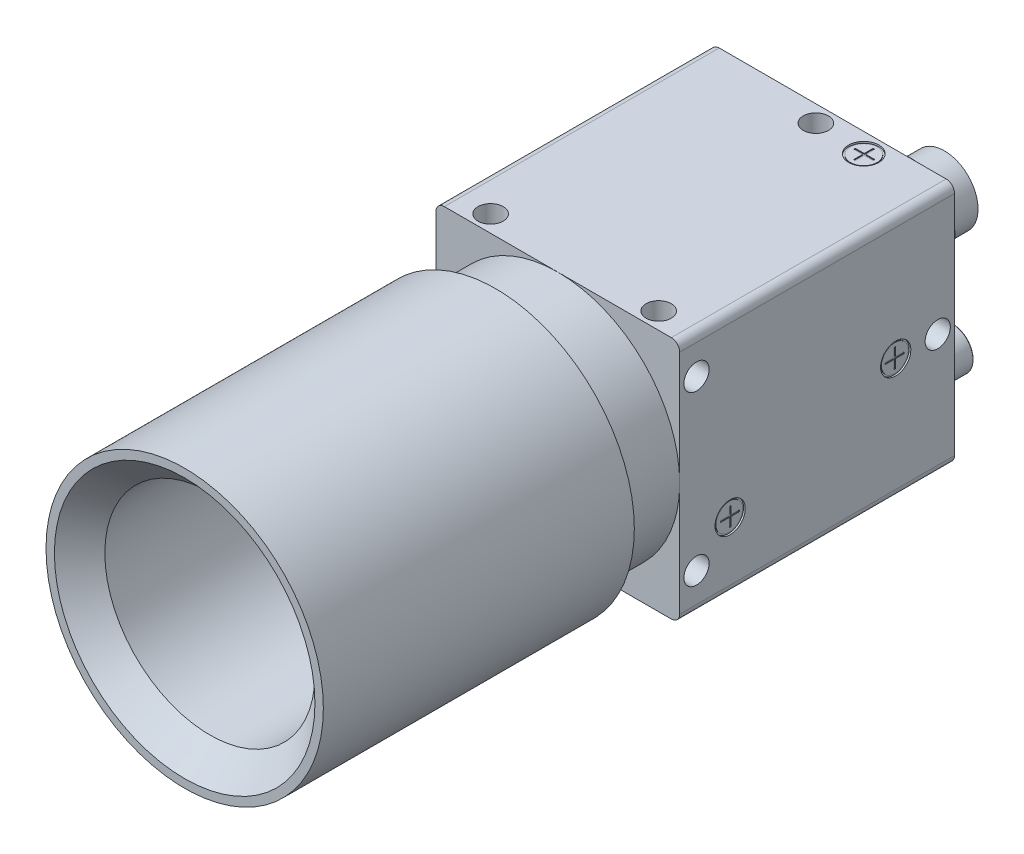
SolidWorks part; units mm, degrees
ref_plane "前视基准面" through (0, 0, 0) normal (0, 0, 1) x (1, 0, 0)
ref_plane "上视基准面" through (0, 0, 0) normal (0, 1, 0) x (1, 0, 0)
ref_plane "右视基准面" through (0, 0, 0) normal (1, 0, 0) x (0, 0, -1)
sketch "草图2" plane through (0, 0, 0) normal (0, 0, 1) x (1, 0, 0)
  line L1 (-14.5, 14.5) -> (14.5, 14.5)
  line L2 (-14.5, 14.5) -> (-14.5, -14.5)
  line L3 (-14.5, -14.5) -> (14.5, -14.5)
  line L4 (14.5, 14.5) -> (14.5, -14.5)
  line L5 (-14.5, 14.5) -> (14.5, -14.5) construction
  line L6 (-14.5, -14.5) -> (14.5, 14.5) construction
  point P0 (0, 0)
  dimension "D1" = 29
  dimension "D2" = 29
extrude "凸台-拉伸1" add sketch "草图2" along normal blind 32.7
sketch "草图3" plane through (0, 0, 32.7) normal (0, 0, 1) x (1, 0, 0)
  circle A0 centre (0, 0) radius 14.5
  circle A1 centre (0, 0) radius 12.5
  dimension "D1" = 29
  dimension "D2" = 25
extrude "凸台-拉伸2" add sketch "草图3" along normal blind 7.4
sketch "草图4" plane through (0, 0, 32.7) normal (0, 0, 1) x (1, 0, 0)
  line L0 (6, 7.5) -> (7.5, 6)
  line L1 (-6, 7.5) -> (6, 7.5)
  line L2 (-7.5, 6) -> (-7.5, -6)
  line L3 (-6, -7.5) -> (6, -7.5)
  line L4 (7.5, 6) -> (7.5, -6)
  line L5 (-6.75, 6.75) -> (6.75, -6.75) construction
  line L6 (-6.75, -6.75) -> (6.75, 6.75) construction
  line L7 (-6, 7.5) -> (-7.5, 6)
  line L8 (0, 0) -> (10.6258, 0) construction
  line L9 (6, -7.5) -> (7.5, -6)
  line L10 (-6, -7.5) -> (-7.5, -6)
  point P0 (0, 0)
  dimension "D1" = 6
  dimension "D2" = 7.5
  dimension "D3" = 6
  dimension "D4" = 45
  dimension "D5" = 45
  dimension "D6" = 7.5
  dimension "D7" = 7.5
extrude "切除-拉伸1" cut sketch "草图4" against normal blind 5
chamfer "倒角1" distance 1 angle 45 8 edges at (-7.5, 0, 32.7) (-6.75, -6.75, 32.7) (0, -7.5, 32.7) (6.75, -6.75, 32.7) (7.5, 0, 32.7) (6.75, 6.75, 32.7) (0, 7.5, 32.7) (-6.75, 6.75, 32.7)
sketch "草图5" plane through (0, 0, 32.7) normal (0, 0, 1) x (1, 0, 0)
  line L0 (6.4142, -8.5) -> (-6.4142, -8.5) construction
  line L5 (-2, -10.5) -> (-2, -12.339)
  line L6 (2, -10.5) -> (2, -12.339)
  arc A0 (2, -10.5) -> (-2, -10.5) centre (0, -10.5) ccw
  circle A1 centre (0, 0) radius 12.5 construction
  circle A2 centre (0, 0) radius 12.5 construction
  arc A3 (-2, -12.339) -> (2, -12.339) centre (0, 0) ccw
  circle M14 centre (0, 0) radius 12.5
extrude "切除-拉伸2" cut sketch "草图5" against normal blind 1 contours L6 A0 L5 M14 region at (0, -10.6598, 32.7)
sketch "草图7" plane through (0, 0, 31.7) normal (0, 0, 1) x (1, 0, 0)
  circle A0 centre (0, -10.5) radius 1.8
  dimension "D1" = 3.6
extrude "凸台-拉伸6" add sketch "草图7" along normal blind 0.8
fillet "圆角1" radius 0.2 1 edges at (1.8, -10.5, 32.5)
sketch "草图8" plane through (0, 0, 32.5) normal (0, 0, 1) x (1, 0, 0)
  line L0 (0, -9.5) -> (0, -11.5)
  line L2 (-1, -10.5) -> (1, -10.5)
  circle A0 centre (0, -10.5) radius 1.6 construction
  point P3 (0, -10.5)
  point P8 (0, -10.5)
  dimension "D1" = 2
  dimension "D2" = 2
extrude "切除-拉伸-薄壁1" cut sketch "草图8" against normal blind 0.2 thin thin type mid plane wall 0.2
fillet "圆角2" radius 0.2 4 edges at (-0.1, -10.6, 32.4) (0.1, -10.6, 32.4) (0.1, -10.4, 32.4) (-0.1, -10.4, 32.4)
fillet "圆角3" radius 0.1 8 edges at (-1, -10.4, 32.4) (-0.1, -11.5, 32.4) (0.1, -11.5, 32.4) (-1, -10.6, 32.4) (1, -10.6, 32.4) (1, -10.4, 32.4) (0.1, -9.5, 32.4) (-0.1, -9.5, 32.4)
mirror "镜向2" about plane through (0, 0, 0) normal (0, 1, 0) of "切除-拉伸2"
mirror "镜向1" about plane through (0, 0, 0) normal (0, 1, 0) of "圆角3", "切除-拉伸-薄壁1", "凸台-拉伸6"
fillet "圆角4" radius 1 4 edges at (-14.5, -14.5, 16.35) (14.5, -14.5, 16.35) (14.5, 14.5, 16.35) (-14.5, 14.5, 16.35)
sketch "草图9" plane through (0, -14.5, 0) normal (0, -1, 0) x (1, 0, 0)
  line L0 (-13.5, 16.35) -> (13.5, 16.35) construction
  line L1 (-13.5, 32.7) -> (-13.5, 0) construction
  line L2 (13.5, 0) -> (13.5, 32.7) construction
  line L3 (0, 0) -> (0, 32.7) construction
  line L4 (0, 32.7) -> (-14.5, 32.7) construction
  circle A0 centre (-10, 2) radius 1.5
  circle A1 centre (-10, 30.7) radius 1.5
  circle A2 centre (10, 30.7) radius 1.5
  circle A3 centre (10, 2) radius 1.5
  dimension "D1" = 3
  dimension "D2" = 28.7
  dimension "D3" = 10
sketch "草图10" plane through (0, -14.5, 0) normal (0, -1, 0) x (1, 0, 0)
  line L0 (-12, 5) -> (12, 5)
  line L1 (-13.5, 32.7) -> (-13.5, 0) construction
  line L3 (-13.5, 0) -> (13.5, 0) construction
  line L5 (-11, 25) -> (11, 25)
  line L6 (-12, 24) -> (-12, 6)
  line L7 (-11, 5) -> (11, 5)
  line L8 (12, 24) -> (12, 6)
  line L9 (-12, 25) -> (12, 5) construction
  line L10 (-12, 5) -> (12, 25) construction
  arc A0 (11, 25) -> (12, 24) centre (11, 24) cw
  arc A1 (-12, 6) -> (-11, 5) centre (-11, 6) ccw
  arc A2 (-11, 25) -> (-12, 24) centre (-11, 24) ccw
  arc A3 (11, 5) -> (12, 6) centre (11, 6) ccw
  point P8 (0, 15)
  dimension "D4" = 1
  dimension "D1" = 5
  dimension "D2" = 1.5
  dimension "D3" = 20
extrude "切除-拉伸4" cut sketch "草图10" against normal blind 0.1 contours L0 A3 L8 A0 L5 A2 L6 A1 region at (0, -14.5, 15)
extrude "切除-拉伸6" cut sketch "草图9" against normal blind 4
sketch "草图12" plane through (0, -14.4, 0) normal (0, -1, 0) x (1, 0, 0)
  line L0 (-11, 5) -> (11, 5) construction
  line L1 (-12, 24) -> (-12, 6) construction
  line L2 (12, 24) -> (12, 6) construction
  line L3 (-11, 5) -> (11, 5) construction
  line L4 (0, 25) -> (0, 32.7) construction
  line L5 (-11, 25) -> (11, 25) construction
  line L6 (0, 32.7) -> (-14.5, 32.7) construction
  circle A0 centre (-10, 7.6) radius 1.8
  circle A1 centre (10, 7.6) radius 1.8
  circle A2 centre (-5, 28.9) radius 1.8
  circle A3 centre (5, 28.9) radius 1.8
  dimension "D1" = 3.6
  dimension "3.6" = 3.6
  dimension "D8" = 3.6
  dimension "D9" = 3.6
  dimension "D2" = 2.6
  dimension "D3" = 2
  dimension "D4" = 2
  dimension "D5" = 2.6
  dimension "D6" = 3.8
  dimension "D7" = 5
extrude "切除-拉伸7" cut sketch "草图12" against normal mid plane 0.4
sketch "草图13" plane through (0, -14.2, 0) normal (0, -1, 0) x (1, 0, 0)
  circle A0 centre (-10, 7.6) radius 1.6
  circle A1 centre (10, 7.6) radius 1.6
  circle A2 centre (5, 28.9) radius 1.6
  circle A3 centre (-5, 28.9) radius 1.6
  dimension "D1" = 3.2
extrude "凸台-拉伸8" add sketch "草图13" along normal blind 0.1
sketch "草图14" plane through (0, -14.3, 0) normal (0, -1, 0) x (1, 0, 0)
  line L0 (-10, 6.3075) -> (-10, 8.7975)
  line L2 (-11.3258, 7.6) -> (-8.7234, 7.6)
extrude "切除-拉伸-薄壁2" cut sketch "草图14" against normal blind 0.1 thin thin type mid plane wall 0.2
mirror "镜向3" about plane through (0, 0, 0) normal (1, 0, 0) of "切除-拉伸-薄壁2"
sketch "草图16" plane through (0, -14.3, 0) normal (0, -1, 0) x (1, 0, 0)
  line L0 (-5, 27.7633) -> (-5, 30.1768)
  line L2 (-6.2768, 28.9) -> (-3.9542, 28.9)
extrude "切除-拉伸-薄壁4" cut sketch "草图16" against normal blind 0.1 thin thin type mid plane wall 0.2
mirror "镜向4" about plane through (0, 0, 0) normal (1, 0, 0) of "切除-拉伸-薄壁4"
sketch "草图17" plane through (14.5, 0, 0) normal (1, 0, 0) x (0, 0, -1)
  line L0 (0, 0) -> (-32.7, 0) construction
  line L1 (-16.35, -13.5) -> (-16.35, 13.5) construction
  line L2 (-32.7, -13.5) -> (0, -13.5) construction
  line L3 (0, 13.5) -> (-32.7, 13.5) construction
  line L4 (-32.7, -13.5) -> (-32.7, 0) construction
  circle A0 centre (-2, 0) radius 1.5
  circle A1 centre (-30.7, -10) radius 1.5
  circle A2 centre (-30.7, 10) radius 1.5
  dimension "D1" = 3
  dimension "D2" = 3
  dimension "D5" = 3
  dimension "D3" = 20
  dimension "D4" = 2
  dimension "D6" = 28.7
extrude "切除-拉伸8" cut sketch "草图17" against normal blind 4
sketch "草图18" plane through (14.5, 0, 0) normal (1, 0, 0) x (0, 0, -1)
  line L0 (-32.7, -13.5) -> (-32.7, 0) construction
  line L1 (-32.7, -13.5) -> (0, -13.5) construction
  circle A0 centre (-7, 0) radius 1.8
  circle A1 centre (-26.7, -6.5) radius 1.8
  dimension "D1" = 3.6
  dimension "D2" = 3.6
  dimension "D3" = 7
  dimension "D4" = 6
  dimension "D5" = 7
extrude "切除-拉伸9" cut sketch "草图18" against normal blind 0.2
sketch "草图19" plane through (14.3, 0, 0) normal (1, 0, 0) x (0, 0, -1)
  circle A0 centre (-7, 0) radius 1.6
  circle A1 centre (-26.7, -6.5) radius 1.6
  dimension "D1" = 3.2
  dimension "D2" = 3.2
extrude "凸台-拉伸9" add sketch "草图19" along normal blind 0.1
sketch "草图20" plane through (14.4, 0, 0) normal (1, 0, 0) x (0, 0, -1)
  line L0 (-5.8853, 0) -> (-8.1622, 0)
  line L1 (-25.498, -6.481) -> (-27.7525, -6.481)
  line L2 (-7.0238, -1.1385) -> (-7.0238, 1.1385)
  line L4 (-26.6033, -7.6281) -> (-26.6033, -5.4574)
extrude "切除-拉伸-薄壁5" cut sketch "草图20" against normal blind 0.1 thin thin type mid plane wall 0.2
mirror "镜向5" about plane through (0, 0, 0) normal (1, 0, 0) of "切除-拉伸9", "凸台-拉伸9", "切除-拉伸-薄壁5"
mirror "镜向6" about plane through (0, 0, 0) normal (1, 0, 0) of "切除-拉伸8"
sketch "草图21" plane through (0, 14.5, 0) normal (0, 1, 0) x (1, 0, 0)
  line L0 (0, 0) -> (0, -32.7) construction
  line L1 (13.5, -32.7) -> (0, -32.7) construction
  line L2 (13.5, -32.7) -> (13.5, 0) construction
  line L3 (13.5, -16.35) -> (-13.5, -16.35) construction
  line L4 (-13.5, 0) -> (-13.5, -32.7) construction
  circle A0 centre (10, -30.7) radius 1.5
  circle A1 centre (-10, -30.7) radius 1.5
  circle A2 centre (0, -2) radius 1.5
  dimension "D1" = 3
  dimension "D2" = 3
  dimension "D3" = 3
  dimension "D4" = 10
  dimension "D5" = 2
  dimension "D6" = 28.7
extrude "切除-拉伸10" cut sketch "草图21" against normal blind 4
sketch "草图22" plane through (0, 14.5, 0) normal (0, 1, 0) x (1, 0, 0)
  line L0 (13.5, 0) -> (-13.5, 0) construction
  line L1 (13.5, -32.7) -> (13.5, 0) construction
  circle A0 centre (6, -2.3) radius 1.8
  dimension "D1" = 3.6
  dimension "D2" = 2.3
  dimension "D3" = 7.5
extrude "切除-拉伸11" cut sketch "草图22" against normal blind 0.2
sketch "草图23" plane through (0, 14.3, 0) normal (0, 1, 0) x (1, 0, 0)
  circle A0 centre (6, -2.3) radius 1.6
  dimension "D1" = 3.2
extrude "凸台-拉伸10" add sketch "草图23" along normal blind 0.1
sketch "草图24" plane through (0, 14.4, 0) normal (0, 1, 0) x (1, 0, 0)
  line L0 (6, -1.0931) -> (6, -3.3966)
  line L2 (7.1517, -2.2448) -> (4.8483, -2.2448)
extrude "切除-拉伸-薄壁6" cut sketch "草图24" against normal blind 0.1 thin thin type mid plane wall 0.2
sketch "草图25" plane through (0, 0, 0) normal (0, 0, -1) x (-1, 0, 0)
  line L0 (13.5, -14.5) -> (-13.5, -14.5) construction
  line L1 (-6.5, 0) -> (6.5, 0)
  line L2 (-7.5, -1) -> (-7.5, -1.1456)
  line L3 (-6.5, -14.5) -> (6.5, -14.5)
  line L4 (7.5, -1) -> (7.5, -1.1456)
  line L5 (-7.5, 0) -> (7.5, -14.5) construction
  line L6 (-7.5, -14.5) -> (7.5, 0) construction
  line L7 (0, 0) -> (0, -7.25) construction
  line L8 (7.5, -13.3544) -> (7.5, -13.5)
  line L9 (0, -7.25) -> (4.0016, -7.25) construction
  line L10 (-7.5, -13.3544) -> (-7.5, -13.5)
  arc A0 (10.2395, -9.6381) -> (10.2395, -4.8619) centre (9.5, -7.25) ccw
  arc A1 (-10.2395, -4.8619) -> (-10.2395, -9.6381) centre (-9.5, -7.25) ccw
  arc A2 (7.5, -1.1456) -> (10.2395, -4.8619) centre (11.3904, -1.1456) ccw
  arc A3 (7.5, -13.3544) -> (10.2395, -9.6381) centre (11.3904, -13.3544) cw
  arc A4 (-7.5, -13.3544) -> (-10.2395, -9.6381) centre (-11.3904, -13.3544) ccw
  arc A5 (-7.5, -1.1456) -> (-10.2395, -4.8619) centre (-11.3904, -1.1456) cw
  arc A6 (-7.5, -13.5) -> (-6.5, -14.5) centre (-6.5, -13.5) ccw
  arc A7 (6.5, -14.5) -> (7.5, -13.5) centre (6.5, -13.5) ccw
  arc A8 (-6.5, 0) -> (-7.5, -1) centre (-6.5, -1) ccw
  arc A9 (6.5, 0) -> (7.5, -1) centre (6.5, -1) cw
  point P0 (0, -7.25)
  dimension "D3" = 5
  dimension "D4" = 1
  dimension "D5" = 3.8904
  dimension "D1" = 15
  dimension "D2" = 19
extrude "凸台-拉伸11" add sketch "草图25" along normal blind 1.5
sketch "草图26" plane through (0, 0, -1.5) normal (0, 0, -1) x (-1, 0, 0)
  line L1 (-5, -2.25) -> (5, -2.25)
  line L2 (-5, -2.25) -> (-5, -12.25)
  line L3 (-5, -12.25) -> (5, -12.25)
  line L4 (5, -2.25) -> (5, -12.25)
  line L5 (-5, -2.25) -> (5, -12.25) construction
  line L6 (-5, -12.25) -> (5, -2.25) construction
  arc A0 (10.2395, -9.6381) -> (10.2395, -4.8619) centre (9.5, -7.25) ccw construction
  point P0 (0, -7.25)
  point P9 (12, -7.25)
  dimension "D1" = 10
  dimension "D2" = 10
extrude "切除-拉伸12" cut sketch "草图26" against normal blind 3
fillet "圆角5" radius 1 4 edges at (5, -12.25, 0) (-5, -12.25, 0) (-5, -2.25, 0) (5, -2.25, 0)
sketch "草图27" plane through (0, 0, -1.5) normal (0, 0, -1) x (-1, 0, 0)
  line L0 (-9.5, -4.75) -> (-5, -4.75)
  line L1 (-5, -3.25) -> (-5, -11.25) construction
  line L2 (-5, -4.75) -> (-5, -9.75)
  line L3 (5, -11.25) -> (5, -3.25) construction
  line L4 (5, -4.75) -> (9.5, -4.75)
  line L5 (5, -4.75) -> (5, -9.75)
  line L6 (9.5, -9.75) -> (5, -9.75)
  line L8 (-5, -3.25) -> (-5, -11.25) construction
  line L9 (-5, -9.75) -> (-9.5, -9.75)
  arc A0 (-9.5, -4.75) -> (-9.5, -9.75) centre (-9.5, -7.25) ccw
  arc A1 (9.5, -9.75) -> (9.5, -4.75) centre (9.5, -7.25) ccw
  dimension "D1" = 5
extrude "凸台-拉伸12" add sketch "草图27" along normal blind 3.3
sketch "草图28" plane through (0, 0, -4.8) normal (0, 0, -1) x (-1, 0, 0)
  circle A0 centre (-9.5, -7.25) radius 1.5
  circle A1 centre (9.5, -7.25) radius 1.5
  dimension "D1" = 3
  dimension "D2" = 3
extrude "切除-拉伸13" cut sketch "草图28" against normal blind 4
chamfer "倒角2" distance 0.1 angle 45 34 edges at (-11, -7.25, -4.8) (-7.25, -9.75, -4.8) (-12, -7.25, -4.8) (-5, -7.25, -4.8) (-7.25, -4.75, -4.8) (7.25, -9.75, -4.8) (12, -7.25, -4.8) (5, -7.25, -4.8) (7.25, -4.75, -4.8) (8, -7.25, -4.8) (5, -10.5, -1.5) (4.7071, -11.9571, -1.5) (0, -12.25, -1.5) (-4.7071, -11.9571, -1.5) (-5, -10.5, -1.5) (-8.2589, -11.0459, -1.5) (-7.5, -13.4272, -1.5) (-7.2071, -14.2071, -1.5) (0, -14.5, -1.5) (7.2071, -14.2071, -1.5) (7.5, -13.4272, -1.5) (8.2589, -11.0459, -1.5) (-5, -4, -1.5) (5, -4, -1.5) (-4.7071, -2.5429, -1.5) (4.7071, -2.5429, -1.5) (0, -2.25, -1.5) (-8.2589, -3.4541, -1.5) (8.2589, -3.4541, -1.5) (-7.5, -1.0728, -1.5) (7.5, -1.0728, -1.5) (-7.2071, -0.2929, -1.5) (7.2071, -0.2929, -1.5) (0, 0, -1.5)
sketch "草图29" plane through (0, 0, 0) normal (0, 0, -1) x (-1, 0, 0)
  line L0 (-14.5, -13.5) -> (-14.5, 13.5) construction
  line L2 (6.5, 0) -> (-6.5, 0) construction
  line L3 (-0.9638, 0) -> (-6.5, 0)
  line L4 (-7.5, -1) -> (-7.5, -1.1456) construction
  line L5 (-7.5, -1) -> (-7.5, -1.1456)
  arc A0 (-3.084, 6.1573) -> (-10.4201, 3.3411) centre (-8, 8) ccw
  arc A2 (-3.084, 6.1573) -> (-0.9638, 0) centre (1.7043, 4.3624) ccw
  arc A3 (-10.4201, 3.3411) -> (-8, -3.0536) centre (-12.7835, -1.2087) cw
  arc A4 (-10.2395, -4.8619) -> (-7.5, -1.1456) centre (-11.3904, -1.1456) ccw construction
  arc A5 (-6.5, 0) -> (-7.5, -1) centre (-6.5, -1) ccw construction
  arc A6 (-6.5, 0) -> (-7.5, -1) centre (-6.5, -1) ccw
  arc A7 (-8, -3.0536) -> (-7.5, -1.1456) centre (-11.3904, -1.1456) ccw
  dimension "D3" = 10.5
  dimension "D1" = 6.5
  dimension "D2" = 6.5
extrude "凸台-拉伸13" add sketch "草图29" along normal blind 1.3
sketch "草图30" plane through (0, 0, -1.3) normal (0, 0, -1) x (-1, 0, 0)
  circle A0 centre (-8, 8) radius 4.5
  dimension "D1" = 9
extrude "切除-拉伸14" cut sketch "草图30" against normal blind 1
sketch "草图31" plane through (0, 0, -0.3) normal (0, 0, -1) x (-1, 0, 0)
  circle A0 centre (-8, 8) radius 4
  circle A1 centre (-8, 8) radius 3.5
  dimension "D1" = 8
  dimension "D2" = 7
extrude "凸台-拉伸14" add sketch "草图31" along normal blind 5
sketch "草图32" plane through (0, 0, 40.1) normal (0, 0, 1) x (1, 0, 0)
  circle A0 centre (0, 0) radius 12.5
  circle A1 centre (0, 0) radius 16.5
  dimension "D1" = 25
  dimension "D2" = 33
extrude "凸台-拉伸15" add sketch "草图32" along normal blind 37
chamfer "倒角3" distance 3 1 edges at (12.5, 0, 77.1)
